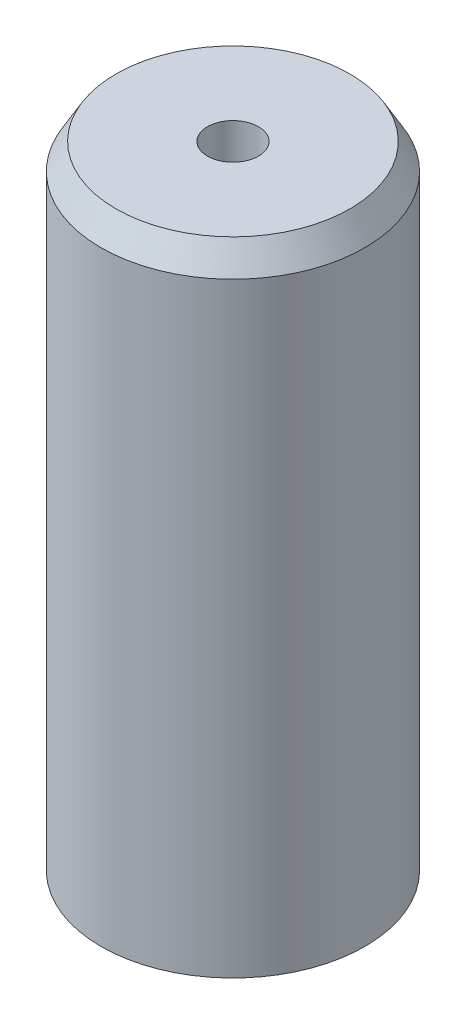
SolidWorks part; units mm, degrees
ref_plane "Front Plane" through (0, 0, 0) normal (0, 0, 1) x (1, 0, 0)
ref_plane "Top Plane" through (0, 0, 0) normal (0, 1, 0) x (1, 0, 0)
ref_plane "Right Plane" through (0, 0, 0) normal (1, 0, 0) x (0, 0, -1)
sketch "Sketch1" plane through (0, 0, 0) normal (0, 1, 0) x (1, 0, 0)
  circle A0 centre (0, 0) radius 5
  dimension "SHAFT_OD" = 10
extrude "Boss-Extrude1" add sketch "Sketch1" along normal blind 24.4844
sketch "Sketch2" plane through (0, 0, 0) normal (0, 1, 0) x (1, 0, 0)
  circle A0 centre (0, 0) radius 0.9667
  dimension "BORE_D" = 1.9334
extrude "Cut-Extrude1" cut sketch "Sketch2" along normal through all
chamfer "Chamfer1" distance 0.9878 angle 30 2 edges at (0, 24.4844, 5) (0, 0, 5) first distance on face at (0, 24.4844, 5) first distance on face at (0, 0, 0.9667)
